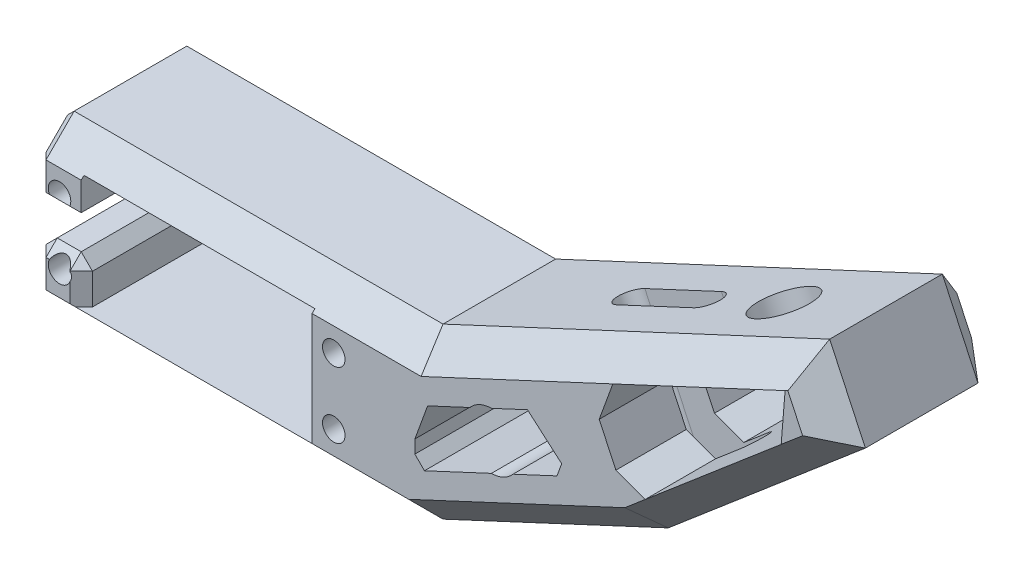
SolidWorks part; units mm, degrees
ref_plane "前视基准面" through (0, 0, 0) normal (0, 0, 1) x (1, 0, 0)
ref_plane "上视基准面" through (0, 0, 0) normal (0, 1, 0) x (1, 0, 0)
ref_plane "右视基准面" through (0, 0, 0) normal (1, 0, 0) x (0, 0, -1)
other "Configuration Table"
sketch "Sketch1" plane through (0, 0, 0) normal (0, 0, 1) x (1, 0, 0)
  line L1 (-28.75, -15) -> (28.75, -15)
  line L2 (-28.75, -15) -> (-28.75, 15)
  line L3 (-28.75, 15) -> (28.75, 15)
  line L4 (28.75, -15) -> (28.75, 15)
  line L5 (-28.75, -15) -> (28.75, 15) construction
  line L6 (-28.75, 15) -> (28.75, -15) construction
  point P0 (0, 0)
  dimension "D1" = 57.5
  dimension "D2" = 30
extrude "Boss-Extrude1" add sketch "Sketch1" along normal blind 30
sketch "Sketch2" plane through (0, 0, 30) normal (0, 0, 1) x (1, 0, 0)
  line L1 (-20.5, -10.5) -> (20.5, -10.5)
  line L2 (-20.5, -10.5) -> (-20.5, 10.5)
  line L3 (-20.5, 10.5) -> (20.5, 10.5)
  line L4 (20.5, -10.5) -> (20.5, 10.5)
  line L5 (-20.5, -10.5) -> (20.5, 10.5) construction
  line L6 (-20.5, 10.5) -> (20.5, -10.5) construction
  point P0 (0, 0)
  dimension "D1" = 41
  dimension "D2" = 21
extrude "Cut-Extrude1" cut sketch "Sketch2" against normal blind 25
ref_plane "Plane1" through (0, 0, 15) normal (0, 0, 1) x (1, 0, 0)
sketch "Sketch8" plane through (0, 0, 30) normal (0, 0, 1) x (1, 0, 0)
  line L0 (0, 0) -> (24.35, 0) construction
  line L1 (24.35, 0) -> (24.35, 5.85) construction
  line L2 (0, 0) -> (0, 15) construction
  line L3 (28.75, 15) -> (-28.75, 15) construction
  circle A0 centre (24.35, 5.85) radius 2
  circle A1 centre (24.35, -5.85) radius 2
  circle A2 centre (-24.35, -5.85) radius 2
  circle A3 centre (-24.35, 5.85) radius 2
  dimension "D3" = 4
  dimension "D1" = 5.85
  dimension "D2" = 24.35
extrude "Cut-Extrude6" cut sketch "Sketch8" against normal blind 10
sketch "Sketch9" plane through (0, 0, 30) normal (0, 0, 1) x (1, 0, 0)
  line L0 (-20.5, 0) -> (-28.75, 0) construction
  line L1 (-20.5, 10.5) -> (-20.5, -10.5) construction
  line L2 (-28.75, 15) -> (-28.75, -15) construction
  line L3 (-28.75, 0) -> (-24.625, 0) construction
  line L5 (-28.75, -3) -> (-20.5, -3)
  line L6 (-28.75, -3) -> (-28.75, 3)
  line L7 (-28.75, 3) -> (-20.5, 3)
  line L8 (-20.5, -3) -> (-20.5, 3)
  line L9 (-28.75, -3) -> (-20.5, 3) construction
  line L10 (-28.75, 3) -> (-20.5, -3) construction
  dimension "D1" = 6
extrude "Cut-Extrude7" cut sketch "Sketch9" against normal blind 25
sketch "Sketch10" plane through (0, 0, 5) normal (0, 0, 1) x (1, 0, 0)
  line L0 (0, 0) -> (-10, 0) construction
  circle A0 centre (-10, 0) radius 5
  dimension "D2" = 10
  dimension "D1" = 10
extrude "Cut-Extrude8" cut sketch "Sketch10" against normal blind 10
sketch "Sketch11" plane through (28.75, 0, 0) normal (1, 0, 0) x (0, 0, -1)
  line L0 (-30, 0) -> (0, 0) construction
  line L1 (-30, -15) -> (-30, 15) construction
  line L2 (0, 0) -> (-15, 0) construction
  line L3 (-15, -15) -> (-15, 15)
  line L4 (-30, 15) -> (0, 15) construction
  line L5 (-15, 15) -> (-11.75, 15)
  line L6 (-11.75, 15) -> (-11.75, 22.5)
  line L7 (-11.75, 22.5) -> (-18.25, 22.5)
  line L8 (-18.25, 22.5) -> (-18.25, 15)
  line L9 (-18.25, 15) -> (-15, 15)
  line L10 (7.5, 3.25) -> (0, 3.25)
  line L11 (0, 3.25) -> (0, 0)
  line L12 (0, -3.25) -> (7.5, -3.25)
  line L13 (0, 0) -> (0, -3.25)
  line L14 (7.5, -3.25) -> (7.5, 3.25)
  line L15 (-11.75, -22.5) -> (-11.75, -15)
  line L16 (-11.75, -15) -> (-15, -15)
  line L17 (-18.25, -15) -> (-18.25, -22.5)
  line L18 (-15, -15) -> (-18.25, -15)
  line L19 (-18.25, -22.5) -> (-11.75, -22.5)
  line L20 (-37.5, -3.25) -> (-30, -3.25)
  line L21 (-30, -3.25) -> (-30, 0)
  line L22 (-30, 3.25) -> (-37.5, 3.25)
  line L23 (-30, 0) -> (-30, 3.25)
  line L24 (-37.5, 3.25) -> (-37.5, -3.25)
  circle A0 centre (-15, 0) radius 7.5 construction
  point P12 (-15, 0)
  point P34 (-15, 0)
  line M5 (0, -15) -> (0, 15)
  line M6 (0, 15) -> (-30, 15)
  line M7 (-30, 15) -> (-30, -15)
  line M8 (-30, -15) -> (0, -15)
  dimension "D1" = 15
  dimension "D2" = 6.5
  dimension "D3" = 7.5
  dimension "D4" = 4
extrude "Boss-Extrude2" [suppressed] add sketch "Sketch11" against normal up to surface (8.75 mm away) contours L22 L24 L20 M7 | L17 L19 L15 M8 | L12 L14 L10 M5 | L7 L8 L6 M6
sketch "Sketch12" plane through (28.75, 0, 0) normal (1, 0, 0) x (0, 0, -1)
  line L20 (-36.5, 15) -> (-30, 15)
  line L21 (-30, -15) -> (-30, -21.5)
  line L22 (0, -15) -> (-11.75, -15)
  line L23 (0, 3.25) -> (0, 15)
  line L40 (0, -15) -> (0, 15)
  line L45 (0, 15) -> (-30, 15)
  line L50 (-30, 15) -> (-30, -15)
  line L55 (-30, -15) -> (0, -15)
  line L60 (0, -15) -> (0, 15)
  line L65 (0, 15) -> (-30, 15)
  line L70 (-30, 15) -> (-30, -15)
  line L75 (-30, -15) -> (0, -15)
  dimension "D1" = 0
extrude "Boss-Extrude3" [suppressed] add sketch "Sketch12" along normal blind 30
sketch "Sketch13" plane through (0, 0, 30) normal (0, 0, 1) x (1, 0, 0)
  line L0 (28.75, 15) -> (38.75, 15)
  line L1 (38.75, 15) -> (107.4107, 47.017)
  line L3 (113.75, 33.4224) -> (78.75, 3.6523)
  line L4 (78.75, 3.6523) -> (38.75, -15)
  line L5 (38.75, -15) -> (28.75, -15)
  line L6 (-28.75, -15) -> (28.75, -15) construction
  line L7 (38.75, 15) -> (38.75, -15) construction
  line L8 (38.75, -15) -> (93.0307, -15) construction
  line L9 (78.75, 3.6523) -> (97.9021, 3.6523) construction
  line L10 (38.75, 15) -> (83.4484, 15) construction
  line L11 (28.75, -15) -> (28.75, 15)
  line L12 (107.4107, 47.017) -> (113.75, 33.4224)
  dimension "D1" = 10
  dimension "D2" = 25
  dimension "D3" = 40
  dimension "D4" = 25
  dimension "D5" = 15
  dimension "D6" = 75
extrude "Boss-Extrude4" add sketch "Sketch13" against normal blind 30
sketch "Sketch15" plane through (0, 0, 30) normal (0, 0, 1) x (1, 0, 0)
  line L0 (38.75, 15) -> (38.75, -15) construction
  line L1 (38.75, -15) -> (38.75, 0) construction
  line L2 (38.75, 0) -> (75.0023, 16.9047) construction
  line L3 (107.4107, 47.017) -> (38.75, 15) construction
  line L4 (38.75, 0) -> (38.75, 5)
  line L5 (38.75, 5) -> (58.75, 14.3262)
  line L7 (38.75, -5) -> (38.75, 0)
  line L8 (38.75, -5) -> (66.25, 7.8235)
  line L9 (66.25, 7.8235) -> (58.75, 14.3262)
  line L10 (38.75, -15) -> (78.75, 3.6523) construction
  line L11 (78.75, 3.6523) -> (67.2593, 28.2941) construction
  line L19 (76.5584, 8.3522) -> (107.6082, 34.7624)
  line L20 (107.6082, 34.7624) -> (104.9923, 40.3724)
  line L21 (104.9923, 40.3724) -> (69.3724, 23.7626)
  line L22 (107.4107, 47.017) -> (38.75, 15)
  line L23 (113.75, 33.4224) -> (107.4107, 47.017)
  line L24 (78.75, 3.6523) -> (113.75, 33.4224)
  line L25 (107.4107, 47.017) -> (38.75, 15)
  line L26 (113.75, 33.4224) -> (107.4107, 47.017)
  line L27 (78.75, 3.6523) -> (113.75, 33.4224)
  line L28 (76.5584, 8.3522) -> (69.3724, 23.7626)
  line L29 (104.9923, 40.3724) -> (40.8631, 10.4685) construction
  line L30 (75.5105, 7.4609) -> (107.6082, 34.7624) construction
  dimension "D1" = 5
  dimension "D2" = 20
  dimension "D3" = 40
  dimension "D4" = 27.5
  dimension "D5" = 0
  dimension "D6" = 5
extrude "Cut-Extrude9" cut sketch "Sketch15" against normal blind 30
chamfer "Chamfer3" distance 5 angle 45 3 edges at (107.6082, 34.7624, 15) (69.3724, 23.7626, 15) (76.5584, 8.3522, 15)
sketch "Sketch16" plane through (1.1757, -2.5212, 0) normal (-0.4226, 0.9063, 0) x (0.9063, 0.4226, 0)
  line L0 (117.2174, -15) -> (97.2174, -15) construction
  line L1 (117.2174, 0) -> (117.2174, -30) construction
  line L2 (-19.7316, -15) -> (19.7316, -15) construction
  line L3 (97.2174, -15) -> (74.7174, -15) construction
  line L4 (67.2174, -15) -> (82.2174, -15) construction
  line L5 (67.2174, -12.5) -> (82.2174, -12.5)
  line L6 (67.2174, -17.5) -> (82.2174, -17.5)
  circle A0 centre (97.2174, -15) radius 5
  arc A1 (67.2174, -12.5) -> (67.2174, -17.5) centre (67.2174, -15) ccw
  arc A2 (82.2174, -17.5) -> (82.2174, -12.5) centre (82.2174, -15) ccw
  point P10 (74.7174, -15)
  dimension "D1" = 10
  dimension "D4" = 2.5
  dimension "D2" = 20
  dimension "D3" = 15
  dimension "D5" = 22.5
extrude "Cut-Extrude10" cut sketch "Sketch16" against normal blind 30
chamfer "Chamfer5" distance 5 angle 45 13 edges at (-28.75, 0, 0) (5, -15, 0) (58.75, -5.6738, 30) (58.75, -5.6738, 0) (96.25, 18.5374, 0) (96.25, 18.5374, 30) (110.5804, 40.2197, 30) (110.5804, 40.2197, 0) (73.0804, 31.0085, 30) (73.0804, 31.0085, 0) (5, 15, 0) (5, -15, 30) (5, 15, 30)
chamfer "Chamfer6" distance 2 angle 45 13 edges at (-28.75, -15, 15) (-28.75, -12.5, 27.5) (-20.5, -6.5, 30) (-28.75, -6.5, 30) (-28.75, -3, 17.5) (-20.5, -3, 17.5) (-24.625, -3, 30) (-28.75, 15, 15) (-28.75, 12.5, 27.5) (-28.75, 6.5, 30) (-20.5, 3, 17.5) (-24.625, 3, 30) (-28.75, 3, 17.5)
chamfer "Chamfer7" distance 2.5 angle 45 1 edges at (-28.75, 0, 5)
chamfer "Chamfer8" distance 2.5 angle 45 3 edges at (66.25, 7.8235, 15) (38.75, 5, 15) (38.75, -5, 15)
sketch "Sketch19" plane through (0, 0, 30) normal (0, 0, 1) x (1, 0, 0)
  line L0 (38.75, 15) -> (38.75, -15) construction
  line L1 (38.75, -15) -> (38.75, 0) construction
  line L2 (38.75, 0) -> (52.3446, 6.3393) construction
  line L3 (62.0953, 25.8861) -> (59.8296, 24.8296) construction
  circle A0 centre (52.3446, 6.3393) radius 5
  dimension "D1" = 10
  dimension "D2" = 15
extrude "Cut-Extrude12" cut sketch "Sketch19" against normal blind 30
sketch "Sketch20" plane through (0, 0, 5) normal (0, 0, 1) x (1, 0, 0)
  circle A0 centre (-10, 0) radius 7.5
  dimension "D1" = 15
extrude "Cut-Extrude13" cut sketch "Sketch20" against normal blind 2.5
